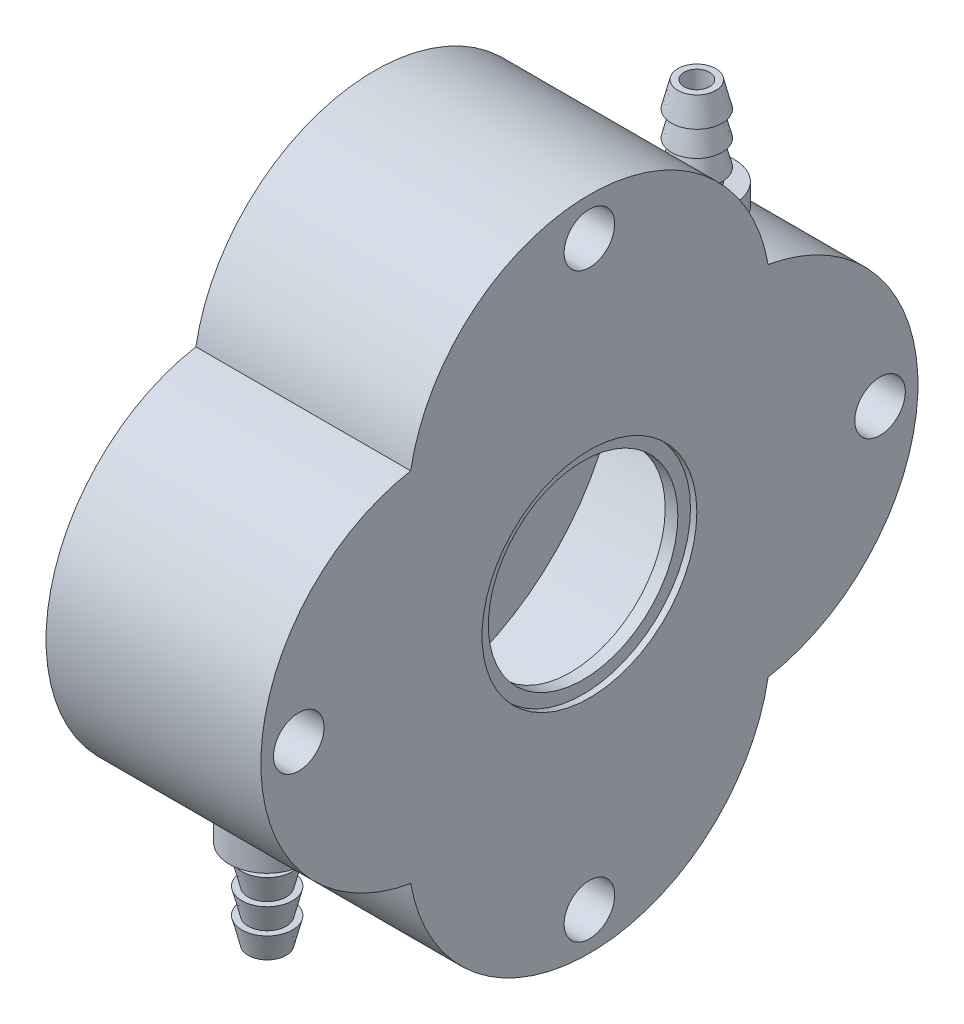
SolidWorks part; units mm, degrees
ref_plane "Front Plane" through (0, 0, 0) normal (0, 0, 1) x (1, 0, 0)
ref_plane "Top Plane" through (0, 0, 0) normal (0, 1, 0) x (1, 0, 0)
ref_plane "Right Plane" through (0, 0, 0) normal (1, 0, 0) x (0, 0, -1)
sketch "Sketch2" plane through (0, 0, 0) normal (1, 0, 0) x (0, 0, -1)
  line L1 (-14.1421, -14.1421) -> (14.1421, -14.1421) construction
  line L2 (-14.1421, -14.1421) -> (-14.1421, 14.1421) construction
  line L3 (-14.1421, 14.1421) -> (14.1421, 14.1421) construction
  line L4 (14.1421, -14.1421) -> (14.1421, 14.1421) construction
  circle A1 centre (0, 23) radius 2
  circle A2 centre (23, 0) radius 2
  circle A3 centre (0, -23) radius 2
  circle A4 centre (-23, 0) radius 2
  circle A5 centre (0, 0) radius 7.5 construction
  circle A6 centre (0, 0) radius 8.5 construction
  circle A10 centre (0, 0) radius 18 construction
  circle A11 centre (0, 0) radius 26 construction
  circle A12 centre (0, -23) radius 3 construction
  circle A14 centre (23, 0) radius 3 construction
  arc A25 (-14.1421, 14.1421) -> (-14.1421, -14.1421) centre (-11.6378, 0) ccw
  arc A26 (-14.1421, -14.1421) -> (14.1421, -14.1421) centre (0, -11.6378) ccw
  circle A27 centre (0, 0) radius 20 construction
  arc A28 (14.1421, 14.1421) -> (-14.1421, 14.1421) centre (0, 11.6378) ccw
  arc A29 (14.1421, -14.1421) -> (14.1421, 14.1421) centre (11.6378, 0) ccw
  point P14 (0, 0)
  point P36 (0, 0)
  point P49 (0, 0)
  dimension "D1" = 36
  dimension "D3" = 4
  dimension "D5" = 15
  dimension "D6" = 17
  dimension "D7" = 52
  dimension "D8" = 40
  dimension "D4" = 23
  dimension "D2" = 4
  dimension "D9" = 4
extrude "Flange" add sketch "Sketch2" along normal mid plane 17
sketch "Sketch10" plane through (8.5, 0, 0) normal (1, 0, 0) x (0, 0, -1)
  circle A0 centre (0, 0) radius 7.5
  dimension "D1" = 15
extrude "Cut-Extrude2" cut sketch "Sketch10" against normal blind 10
sketch "Sketch3" plane through (8.5, 0, 0) normal (1, 0, 0) x (0, 0, -1)
  circle A0 centre (0, 0) radius 8.5
  dimension "D1" = 17
extrude "O-Ring Seat" cut sketch "Sketch3" against normal blind 0.5
sketch "Sketch8" plane through (0, 0, 0) normal (-1, 0, 0) x (0, 0, 1)
  circle A0 centre (0, 0) radius 18
  dimension "D1" = 36
extrude "Cut-Extrude1" cut sketch "Sketch8" against normal mid plane 14
sketch "Sketch5" plane through (0, 0, 0) normal (0, 1, 0) x (1, 0, 0)
  line L1 (0, -28.6) -> (0, 28.6) construction
  circle A0 centre (0, 17) radius 1
  dimension "D1" = 2
  dimension "D2" = 17
extrude "Outlet" cut sketch "Sketch5" along normal through all
ref_plane "Plane2" through (0, 14.1421, 0) normal (0, 1, 0) x (1, 0, 0)
sketch "Sketch6" plane through (0, 14.1421, 0) normal (0, 1, 0) x (1, 0, 0)
  circle A2 centre (0, 17) radius 1
  circle A3 centre (0, 17) radius 3
  dimension "D1" = 2
extrude "Boss-Extrude2" add sketch "Sketch6" against normal up to next
ref_axis "Axis1" through (0, 14.1421, -17) along (0, -1, 0)
sketch "Sketch9" plane through (0, 0, 0) normal (1, 0, 0) x (0, 0, -1)
  line L0 (18, 14.1421) -> (18, 21.1421)
  line L1 (18, 21.1421) -> (18.5, 21.1421)
  line L2 (18.5, 21.1421) -> (19, 19.1421)
  line L3 (19, 19.1421) -> (18.5, 19.1421)
  line L4 (18.5, 19.1421) -> (19, 17.1421)
  line L5 (19, 17.1421) -> (18.5, 17.1421)
  line L6 (18.5, 17.1421) -> (19, 15.1421)
  line L7 (19, 15.1421) -> (18.5, 15.1421)
  line L8 (18.5, 15.1421) -> (18.5, 14.1421)
  line L9 (18.5, 14.1421) -> (18, 14.1421)
  line L10 (17, 14.1421) -> (17, -0.6906) construction
  line L11 (20, 14.1421) -> (14.1421, 14.1421) construction
  dimension "D1" = 0.5
  dimension "D2" = 0.5
  dimension "D3" = 2
  dimension "D4" = 1
  dimension "D5" = 1
revolve "Revolve1" add sketch "Sketch9" angle 360 about axis through (0, 14.1421, -17) along (0, -1, 0)
pattern_circular "Inlet" count 2 every 180 about axis through (8, 0, 0) along (-1, 0, 0) of "Boss-Extrude2", "Revolve1", "Outlet"
sketch "Sketch11" plane through (-7, 0, 0) normal (1, 0, 0) x (0, 0, -1)
  line L1 (-5.3033, 5.3033) -> (5.3033, 5.3033)
  line L2 (-5.3033, 5.3033) -> (-5.3033, -5.3033)
  line L3 (-5.3033, -5.3033) -> (5.3033, -5.3033)
  line L4 (5.3033, 5.3033) -> (5.3033, -5.3033)
  circle A0 centre (0, 0) radius 7.5 construction
  dimension "D1" = 15
extrude "Cut-Extrude3" cut sketch "Sketch11" against normal blind 0.5
sketch "Sketch12" plane through (-7.5, 0, 0) normal (1, 0, 0) x (0, 0, -1)
  line L0 (-4.8033, -4.8033) -> (4.8033, 4.8033) construction
  line L1 (5.3033, -5.3033) -> (5.3033, 5.3033) construction
  line L2 (5.3033, 5.3033) -> (-5.3033, 5.3033) construction
  circle A0 centre (4.8033, 4.8033) radius 0.5
  circle A1 centre (-4.8033, -4.8033) radius 0.5
  dimension "D1" = 1
extrude "Cut-Extrude4" cut sketch "Sketch12" against normal through all
chamfer "Chamfer1" distance 1 angle 45 2 edges at (-8.5, -4.8033, 4.3033) (-8.5, 4.8033, -5.3033)
